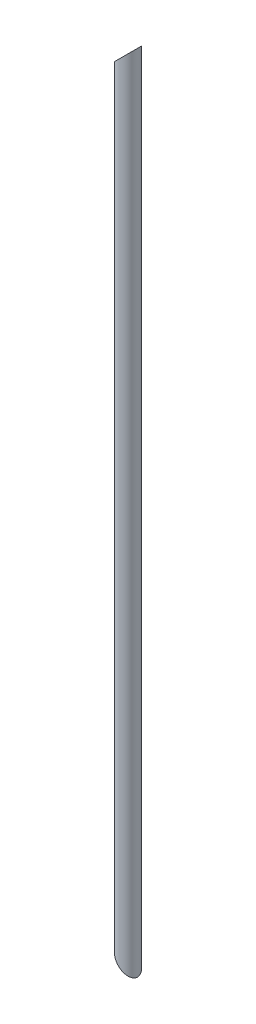
SolidWorks part; units mm, degrees
ref_plane "Plano frontal" through (0, 0, 0) normal (0, 0, 1) x (1, 0, 0)
ref_plane "Plano superior" through (0, 0, 0) normal (0, 1, 0) x (1, 0, 0)
ref_plane "Plano direito" through (0, 0, 0) normal (1, 0, 0) x (0, 0, -1)
sketch "Esboço2" plane through (0, 0, 0) normal (0, 0, 1) x (1, 0, 0)
  line L0 (0, 0) -> (0, 2670) construction
  line L1 (31.75, 0) -> (31.75, 2670)
  line L2 (31.75, 2670) -> (0, 2670)
  line L3 (31.75, 0) -> (0, 0)
  line L4 (0, 0) -> (0, 2670)
  dimension "D1" = 31.75
  dimension "D2" = 2670
revolve "Revolução2" add sketch "Esboço2" angle 360 about L0
sketch "Esboço3" plane through (0, 0, 0) normal (0, 0, 1) x (1, 0, 0)
  line L0 (-31.75, 2670) -> (31.75, 2670)
  line L1 (31.75, 2670) -> (-31.75, 2606.5)
  line L2 (-31.75, 2670) -> (-31.75, 0) construction
  line L3 (-31.75, 2606.5) -> (-31.75, 2670)
  line L4 (31.75, 0) -> (-31.75, 63.5)
  line L8 (-31.75, 63.5) -> (-31.75, 0)
  line L9 (-31.75, 0) -> (31.75, 0)
extrude "Corte-extrusão1" cut sketch "Esboço3" against normal through all both and the other way through all
sketch "Esboço9" plane through (0, 0, 0) normal (0, 1, 0) x (1, 0, 0)
  circle A0 centre (0, 0) radius 30.75
  dimension "D1" = 61.5
extrude "Corte-extrusão6" cut sketch "Esboço9" along normal through all
sketch "Esboço10" plane through (15.875, 15.875, 0) normal (-0.7071, -0.7071, 0) x (0, 0, 1)
  line L0 (0, 67.3519) -> (0, -22.4506) construction
  ellipse E0 centre (0, 22.4506) end of major axis (0, 67.3519) minor radius 31.75 construction
  point P9 (0, 22.4506)
